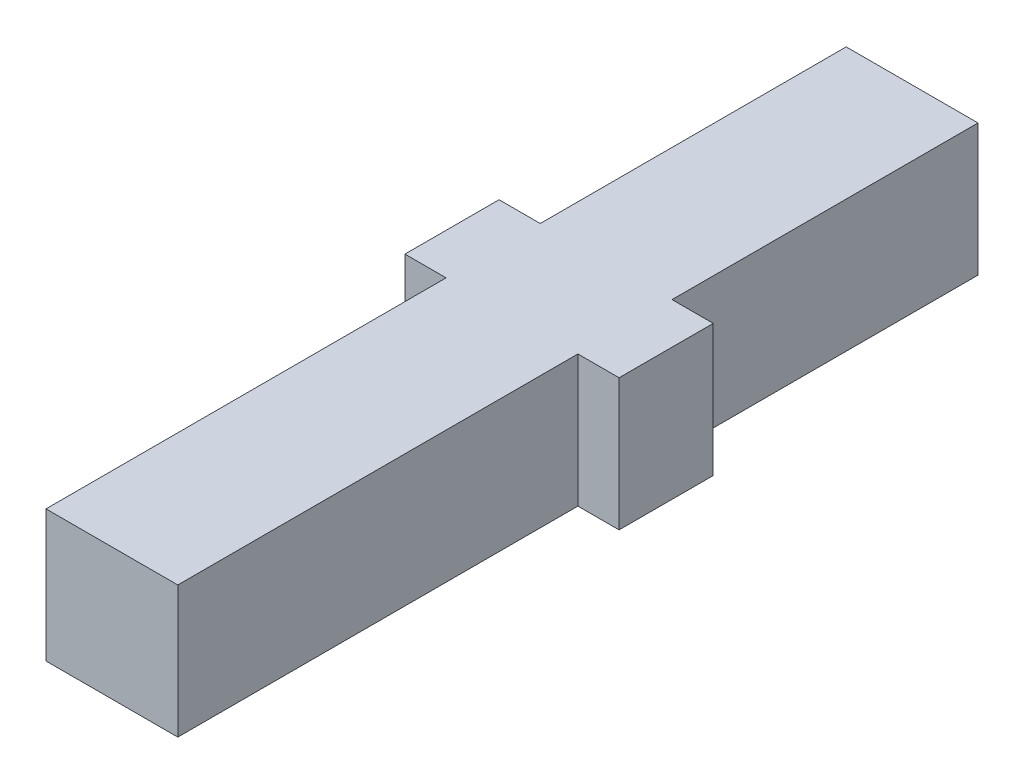
SolidWorks part; units mm, degrees
ref_plane "Front Plane" through (0, 0, 0) normal (0, 0, 1) x (1, 0, 0)
ref_plane "Top Plane" through (0, 0, 0) normal (0, 1, 0) x (1, 0, 0)
ref_plane "Right Plane" through (0, 0, 0) normal (1, 0, 0) x (0, 0, -1)
sketch "Sketch1" plane through (0, 0, 0) normal (0, 0, 1) x (1, 0, 0)
  line L5 (0.875, 0) -> (3.875, 0) construction
  line L6 (0.875, 0) -> (0.875, 3) construction
  line L7 (0.875, 3) -> (3.875, 3) construction
  line L8 (3.875, 0) -> (3.875, 3) construction
  line L10 (0, 0) -> (4.75, 0) construction
  line L14 (0, 0) -> (0, 3) construction
  line L15 (0, 3) -> (4.75, 3) construction
  line L16 (4.75, 0) -> (4.75, 3) construction
  line L36 (0.1, 0.1) -> (4.65, 0.1)
  line L37 (4.65, 0.1) -> (4.65, 2.9)
  line L38 (0.1, 2.9) -> (4.65, 2.9)
  line L39 (0.1, 0.1) -> (0.1, 2.9)
  line L40 (0.975, 0.1) -> (3.775, 0.1)
  line L41 (3.775, 0.1) -> (3.775, 2.9)
  line L42 (0.975, 2.9) -> (3.775, 2.9)
  line L43 (0.975, 0.1) -> (0.975, 2.9)
  point P0 (2.375, 0)
  point P1 (2.375, 0)
  point P2 (0, 0)
  point P40 (-34.686, 12.7573)
  dimension "D1" = 3
  dimension "D2" = 4.75
  dimension "D3" = 3
  dimension "D4" = 3
  dimension "D5" = 0.1
  dimension "D6" = 0.1
extrude "Boss-Extrude1" add sketch "Sketch1" along normal blind 17 contours L43 L42 L41 L40
extrude "Boss-Extrude2" add sketch "Sketch1<3>" along normal blind 2 from offset 6.5 contours L37 L38 L39 L36
sketch "Sketch1<3>" plane through (0, 0, 0) normal (0, 0, 1) x (1, 0, 0) same geometry as "Sketch1"
